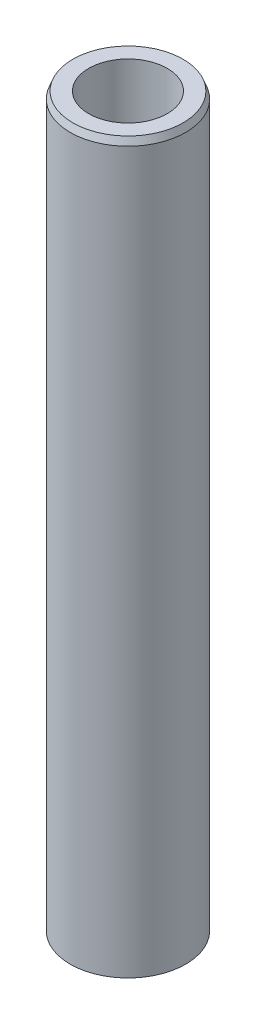
SolidWorks part; units mm, degrees
ref_plane "Front Plane" through (0, 0, 0) normal (0, 0, 1) x (1, 0, 0)
ref_plane "Top Plane" through (0, 0, 0) normal (0, 1, 0) x (1, 0, 0)
ref_plane "Right Plane" through (0, 0, 0) normal (1, 0, 0) x (0, 0, -1)
sketch "Sketch1" plane through (0, 0, 0) normal (0, 1, 0) x (1, 0, 0)
  circle A0 centre (0, 0) radius 47.5
  dimension "SHAFT_OD" = 95
extrude "Boss-Extrude1" add sketch "Sketch1" along normal blind 600
sketch "Sketch2" plane through (0, 0, 0) normal (0, 1, 0) x (1, 0, 0)
  circle A0 centre (0, 0) radius 32.2943
  dimension "BORE_D" = 64.5886
extrude "Cut-Extrude1" cut sketch "Sketch2" along normal through all
chamfer "Chamfer1" distance 5.7358 angle 20.834 2 edges at (0, 600, 47.5) (0, 0, 47.5) first distance on face at (0, 600, 47.5) first distance on face at (0, 0, 32.2943)
